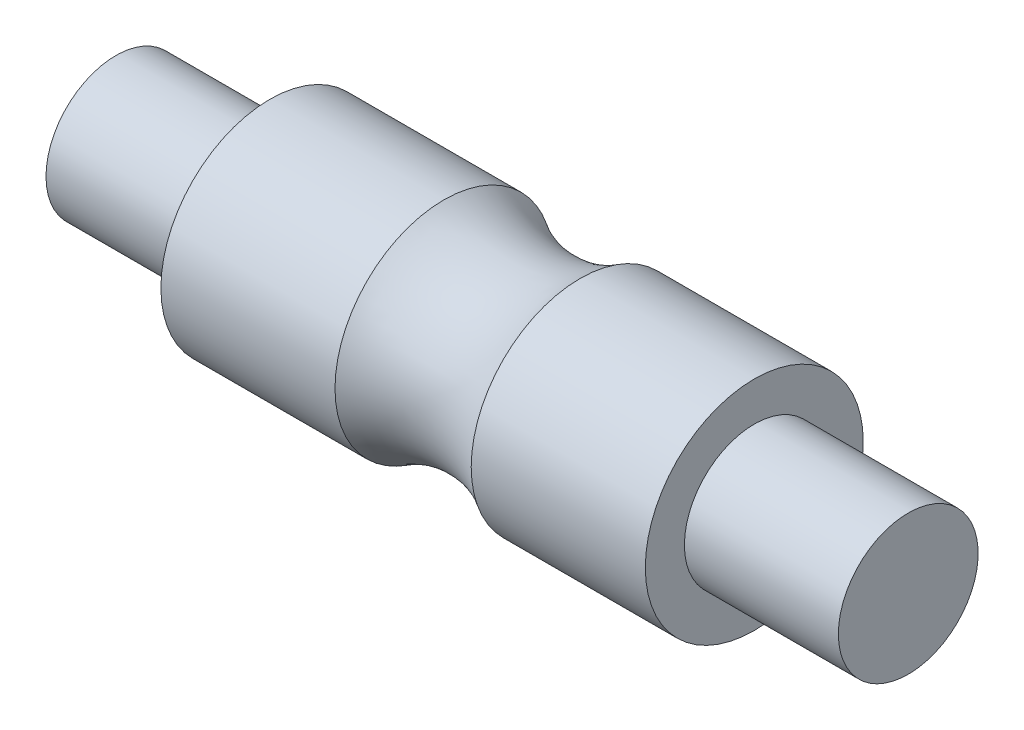
SolidWorks part; units mm, degrees
material "Chrome Stainless Steel"
ref_plane "Front Plane" through (0, 0, 0) normal (0, 0, 1) x (1, 0, 0)
ref_plane "Top Plane" through (0, 0, 0) normal (0, 1, 0) x (1, 0, 0)
ref_plane "Right Plane" through (0, 0, 0) normal (1, 0, 0) x (0, 0, -1)
ref_axis "X-axis" through (-88.99, 0, 0) along (1, 0, 0)
ref_axis "Y-axis" through (0, -55, 0) along (0, 1, 0)
ref_axis "Z-axis" through (0, 0, 55) along (0, 0, -1)
sketch "Sketch1" plane through (0, 0, 0) normal (0, 0, 1) x (1, 0, 0)
  line L0 (-9.9056, 0) -> (12.1876, 0) construction
  line L1 (0, 0) -> (8.4963, 0)
  line L2 (8.4963, 0) -> (8.4963, 1.4986)
  line L3 (8.4963, 1.4986) -> (5.1943, 1.4986)
  line L4 (5.1943, 1.4986) -> (5.1943, 2.3368)
  line L5 (5.1943, 2.3368) -> (1.4605, 2.3368)
  line L6 (0, 1.905) -> (0, 0)
  line L7 (0, 4.2978) -> (0, -4.9199) construction
  line L8 (-1.6418, 1.905) -> (-0.699, 1.905) construction
  arc A0 (1.4605, 2.3368) -> (0, 1.905) centre (0, 4.5909) cw
  point P13 (2.7331, 2.3368)
  dimension "D1" = 16.9926
  dimension "D2" = 2.9972
  dimension "D3" = 4.6736
  dimension "D4" = 3.81
  dimension "D5" = 2.921
  dimension "D6" = 10.3886
revolve "Revolve1" add sketch "Sketch1" angle 360 about L0
mirror "Mirror1" about plane through (0, 0, 0) normal (1, 0, 0) of "Revolve1"
